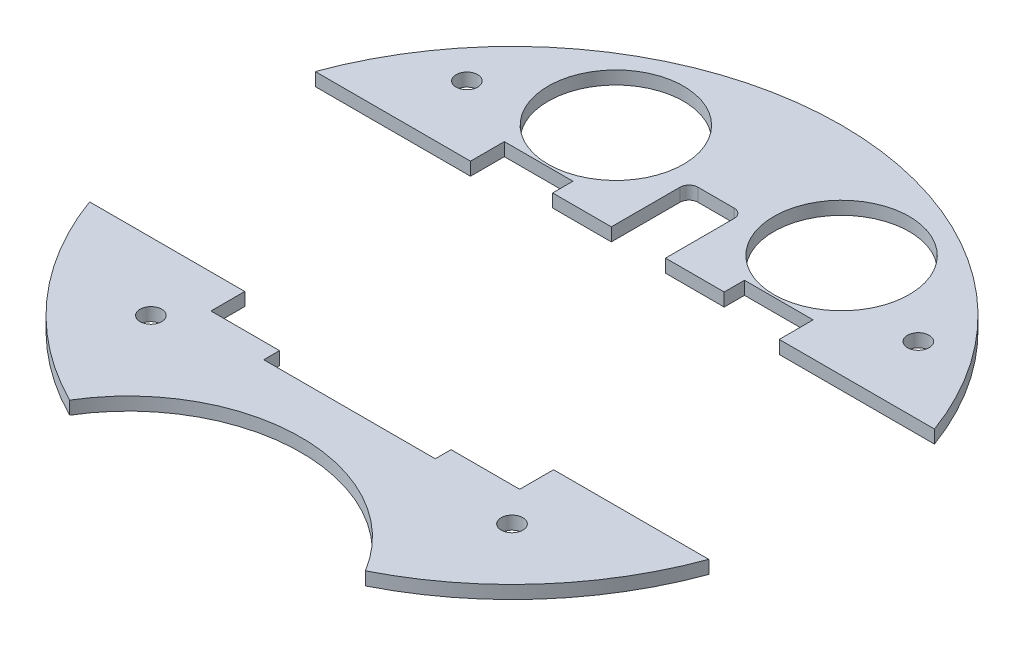
SolidWorks part; units mm, degrees
material "ABS"
ref_plane "Front Plane" through (0, 0, 0) normal (0, 0, 1) x (1, 0, 0)
ref_plane "Top Plane" through (0, 0, 0) normal (0, 1, 0) x (1, 0, 0)
ref_plane "Right Plane" through (0, 0, 0) normal (1, 0, 0) x (0, 0, -1)
sketch "Sketch1" plane through (0, 0, 0) normal (0, 1, 0) x (1, 0, 0)
  line L0 (0, -85) -> (-32.7511, -65.2408) construction
  line L1 (0, -85) -> (0, 0) construction
  arc A0 (32.7511, -65.2408) -> (-32.7511, -65.2408) centre (0, 0) ccw
  arc A1 (32.7511, -65.2408) -> (-32.7511, -65.2408) centre (0, -85) ccw
  dimension "D1" = 146
  dimension "D2" = 76.5
  dimension "D3" = 85
extrude "Boss-Extrude1" add sketch "Sketch1" along normal blind 2.9
sketch "solenoid placement" plane through (0, 2.9, 0) normal (0, 1, 0) x (1, 0, 0)
  line L4 (-19, -36) -> (19, -36)
  line L5 (-19, 28) -> (-19, -36)
  line L10 (19, 28) -> (-19, 28)
  line L11 (19, -36) -> (19, 28)
  line L12 (-19, -36) -> (19, -36)
  line L13 (-19, 28) -> (-19, -36)
  line L14 (19, 28) -> (-19, 28)
  line L15 (19, -36) -> (19, 28)
  dimension "D1" = 0
extrude "Cut-Extrude1" cut sketch "solenoid placement" against normal through all
sketch "Sketch7" plane through (0, 2.9, 0) normal (0, 1, 0) x (1, 0, 0)
  circle A3 centre (25, 48) radius 15
  circle A4 centre (25, 48) radius 15
  circle A5 centre (-25, 48) radius 15
  circle A6 centre (-25, 48) radius 15
  dimension "D1" = 0
  dimension "D2" = 0
extrude "Cut-Extrude6" cut sketch "Sketch7" against normal through all
sketch "Sketch8" plane through (0, 2.9, 0) normal (0, 1, 0) x (1, 0, 0)
  circle A1 centre (40, -40) radius 2.4
  circle A2 centre (40, -40) radius 2.4
  circle A3 centre (-40, -40) radius 2.4
  circle A4 centre (-40, -40) radius 2.4
  circle A5 centre (-50, 40) radius 2.4
  circle A6 centre (-50, 40) radius 2.4
  circle A7 centre (50, 40) radius 2.4
  circle A8 centre (50, 40) radius 2.4
  dimension "D1" = 0
  dimension "D2" = 0
  dimension "D3" = 0
  dimension "D4" = 0
extrude "Cut-Extrude7" cut sketch "Sketch8" against normal through all
sketch "Sketch3" plane through (0, 2.9, 0) normal (0, 1, 0) x (1, 0, 0)
  line L1 (-34.2, -32.5) -> (-22.2, -32.5)
  line L2 (-34.2, 25) -> (-68.5857, 25)
  line L3 (-34.2, 32.5) -> (-22.2, 32.5)
  line L4 (-22.2, -32.5) -> (-22.2, 32.5) construction
  line L8 (0, 0) -> (0, 73) construction
  line L17 (-34.2, -32.5) -> (-34.2, -25)
  line L18 (-34.2, -25) -> (-68.5857, -25)
  line L19 (-34.2, 25) -> (-34.2, 32.5)
  line L21 (-22.2, 32.5) -> (-19, 32.5)
  line L22 (-22.2, 32.5) -> (-22.2, -32.5) construction
  line L23 (-22.2, -32.5) -> (-19, -32.5)
  line L24 (-19, 32.5) -> (-19, -32.5)
  line L25 (22.2, 32.5) -> (22.2, -32.5) construction
  line L26 (22.2, -32.5) -> (22.2, 32.5) construction
  line L27 (19, 32.5) -> (19, -32.5)
  line L28 (22.2, -32.5) -> (19, -32.5)
  line L29 (22.2, 32.5) -> (19, 32.5)
  line L30 (34.2, 25) -> (34.2, 32.5)
  line L31 (34.2, -25) -> (68.5857, -25)
  line L32 (34.2, -32.5) -> (34.2, -25)
  line L33 (34.2, 32.5) -> (22.2, 32.5)
  line L34 (34.2, 25) -> (68.5857, 25)
  line L35 (34.2, -32.5) -> (22.2, -32.5)
  line L36 (-19, 28) -> (-19, -36) construction
  arc A0 (32.7511, -65.2408) -> (-32.7511, -65.2408) centre (0, 0) ccw construction
  arc A2 (68.5857, 25) -> (68.5857, -25) centre (0, 0) cw
  arc A3 (-68.5857, 25) -> (-68.5857, -25) centre (0, 0) ccw
  point P13 (-19, -32.5)
  point P17 (0, 0)
  point P31 (-34.2, -32.5)
  dimension "D1" = 50
extrude "Cut-Extrude3" cut sketch "Sketch3" against normal through all
sketch "Sketch9" plane through (0, 2.9, 0) normal (0, 1, 0) x (1, 0, 0)
  line L0 (6, 43.2) -> (6, 28)
  line L1 (-6, 43.2) -> (-6, 28)
  line L2 (13, 43.2) -> (6, 43.2) construction
  line L3 (-13, 43.2) -> (-6, 43.2) construction
  line L4 (-13, 28) -> (13, 28)
  line L5 (13, 28) -> (13, 43.2)
  line L6 (11, 45.2) -> (-11, 45.2)
  line L7 (-13, 43.2) -> (-13, 28)
  line L8 (-6, 28) -> (6, 28)
  line L9 (13, 28) -> (13, 43.2) construction
  line L10 (4, 45.2) -> (-4, 45.2)
  line L11 (-13, 43.2) -> (-13, 28) construction
  arc A0 (-6, 43.2) -> (-4, 45.2) centre (-4, 43.2) cw
  arc A1 (6, 43.2) -> (4, 45.2) centre (4, 43.2) ccw
  arc A2 (13, 43.2) -> (11, 45.2) centre (11, 43.2) ccw
  arc A3 (-11, 45.2) -> (-13, 43.2) centre (-11, 43.2) ccw
  point P16 (-6, 45.2)
  point P19 (6, 45.2)
  dimension "D3" = 2
  dimension "D2" = 12
  dimension "D1" = 0
extrude "Cut-Extrude8" cut sketch "Sketch9" against normal through all
equation "\"smallPulleyTeeth\"= 15"
equation "\"largePulleyTeeth\"= 30"
equation "\"eighthThick\"= 2.9mm"
equation "\"sixteenthThick\" = 1.7mm"
equation "\"quarterThick\"=6.0mm"
equation "\"OD\" = 146mm"
equation "\"puckAngle\" = 60.5deg"
equation "\"D1@Sketch1\"=\"OD\""
equation "\"puckDiam\" = 76.5mm"
equation "\"D2@Sketch1\"=\"puckDiam\""
equation "\"D1@Boss-Extrude1\"=\"eighthThick\""
equation "\"axlePress\" = 5.9mm"
equation "\"press\" = 0.2mm"
equation "\"wheelClear\" = 0.3mm"
equation "\"10-32clear\" = 4.8mm"
equation "\"6-32clear\" = 3.3mm"
equation "\"8-32clear\" = 4.0mm"
equation "\"4-40clear\" = 3.0mm"
equation "\"wheelHeight\" = 22mm"
equation "\"wheelWell\" = 65mm"
equation "\"puckDist\" = 85mm"
equation "\"D3@Sketch1\"=\"puckDist\""
equation "\"scoopFillet\" = 5mm"
